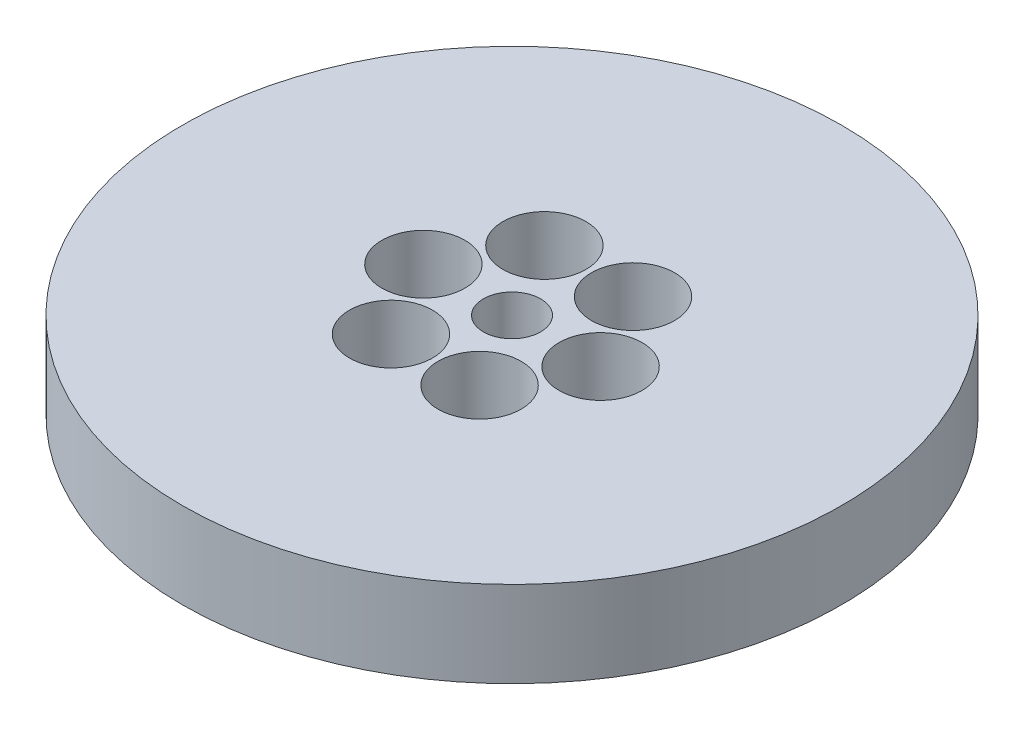
SolidWorks part; units mm, degrees
ref_plane "Front Plane" through (0, 0, 0) normal (0, 0, 1) x (1, 0, 0)
ref_plane "Top Plane" through (0, 0, 0) normal (0, 1, 0) x (1, 0, 0)
ref_plane "Right Plane" through (0, 0, 0) normal (1, 0, 0) x (0, 0, -1)
sketch "Sketch1" plane through (0, 0, 0) normal (0, 1, 0) x (1, 0, 0)
  circle A0 centre (0, 0) radius 57.5
  dimension "FLANGE_OD" = 115
extrude "Boss-Extrude1" add sketch "Sketch1" along normal blind 15
sketch "Sketch2" plane through (0, 0, 0) normal (0, 1, 0) x (1, 0, 0)
  circle A0 centre (0, 0) radius 5
  dimension "BORE_D" = 10
extrude "Cut-Extrude1" cut sketch "Sketch2" along normal through all
sketch "Sketch3" plane through (0, 15, 0) normal (0, 1, 0) x (1, 0, 0)
  circle A0 centre (0, 0) radius 15.4575 construction
  circle A1 centre (-15.4575, 0) radius 7.2482
  dimension "BOLT_D" = 14.4963
  dimension "BOLT_PCD" = 30.9149
extrude "Cut-Extrude2" cut sketch "Sketch3" against normal blind 14.2633
pattern_circular "CirPattern1" count 6 over 360 about axis through (0, 0, 0) along (0, 1, 0) of "Cut-Extrude2"
